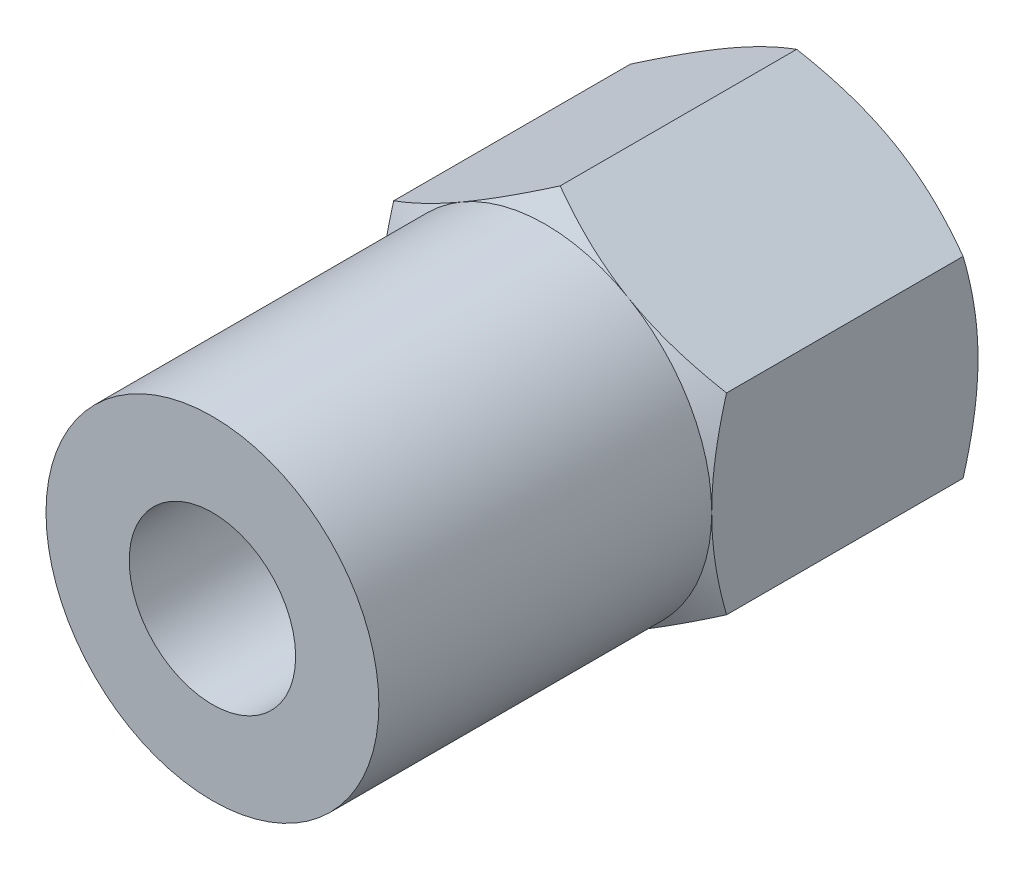
SolidWorks part; units mm, degrees
material "Brass"
ref_plane "Front Plane" through (0, 0, 0) normal (0, 0, 1) x (1, 0, 0)
ref_plane "Top Plane" through (0, 0, 0) normal (0, 1, 0) x (1, 0, 0)
ref_plane "Right Plane" through (0, 0, 0) normal (1, 0, 0) x (0, 0, -1)
sketch "Sketch1" plane through (0, 0, 0) normal (0, 0, 1) x (1, 0, 0)
  line L1 (0, 2.8868) -> (-2.5, 1.4434)
  line L2 (-2.5, 1.4434) -> (-2.5, -1.4434)
  line L3 (-2.5, -1.4434) -> (0, -2.8868)
  line L4 (0, -2.8868) -> (2.5, -1.4434)
  line L5 (2.5, -1.4434) -> (2.5, 1.4434)
  line L6 (2.5, 1.4434) -> (0, 2.8868)
  circle A0 centre (0, 0) radius 2.5 construction
  dimension "D1" = 5
extrude "Boss-Extrude1" add sketch "Sketch1" along normal blind 4
hole_wizard "M3x0.5 Tapped Hole1" positions "Sketch3" profile "Sketch2" tap size "M3x0.5" standard "Ansi Metric"
sketch "Sketch3" plane through (0, 0, 4) normal (0, 0, 1) x (1, 0, 0)
  point P0 (0, 0)
sketch "Sketch2" plane through (0, 0, 4) normal (1, 0, 0) x (0, -1, 0)
  line L0 (0, 0) -> (0, 8.2511)
  line L1 (0, 8.2511) -> (1.25, 7.5)
  line L2 (1.25, 7.5) -> (1.25, 0)
  line L5 (1.25, 0) -> (0, 0)
  line L10 (0, 8.2511) -> (-1.25, 7.5) construction
  line L11 (0, -6.35) -> (0, 107.95) construction
  dimension "Tap Drill Dia." = 2.5
  dimension "Tap Drill Depth" = 7.5
  dimension "Drill Angle" = 118
sketch "Sketch4" plane through (0, 0, 0) normal (1, 0, 0) x (0, 0, -1)
  line L0 (-3.7767, 2.8868) -> (-4, 2.5)
  line L1 (-4, 2.8868) -> (0, 2.8868) construction
  line L2 (-4, 1.4434) -> (-4, 2.8868) construction
  line L3 (-4, 2.5) -> (-4, 2.8868)
  line L4 (-4, 2.8868) -> (-3.7767, 2.8868)
  line L5 (0, 0) -> (-2, 0) construction
  line L6 (-2, 0) -> (-2, 2.8868) construction
  line L8 (0, 2.8868) -> (-0.2233, 2.8868)
  line L9 (0, 2.5) -> (0, 2.8868)
  line L10 (-0.2233, 2.8868) -> (0, 2.5)
  dimension "D1" = 30
  dimension "D2" = 5
revolve "Cut-Revolve1" cut sketch "Sketch4" angle 360 about L5
sketch "Sketch5" plane through (0, 0, 4) normal (0, 0, 1) x (1, 0, 0)
  circle A0 centre (0, 0) radius 1.25 construction
  circle A1 centre (0, 0) radius 1.25
  arc A6 (1.25, -2.1651) -> (2.5, 0) centre (0, 0) ccw
  arc A7 (2.5, 0) -> (1.25, 2.1651) centre (0, 0) ccw
  arc A8 (1.25, 2.1651) -> (-1.25, 2.1651) centre (0, 0) ccw
  arc A9 (-1.25, 2.1651) -> (-2.5, 0) centre (0, 0) ccw
  arc A10 (-2.5, 0) -> (-1.25, -2.1651) centre (0, 0) ccw
  arc A11 (-1.25, -2.1651) -> (1.25, -2.1651) centre (0, 0) ccw
  arc A12 (1.25, -2.1651) -> (2.5, 0) centre (0, 0) ccw
  arc A13 (2.5, 0) -> (1.25, 2.1651) centre (0, 0) ccw
  arc A14 (1.25, 2.1651) -> (-1.25, 2.1651) centre (0, 0) ccw
  arc A15 (-1.25, 2.1651) -> (-2.5, 0) centre (0, 0) ccw
  arc A16 (-2.5, 0) -> (-1.25, -2.1651) centre (0, 0) ccw
  arc A17 (-1.25, -2.1651) -> (1.25, -2.1651) centre (0, 0) ccw
  dimension "D1" = 0
extrude "Boss-Extrude2" add sketch "Sketch5" along normal blind 5
